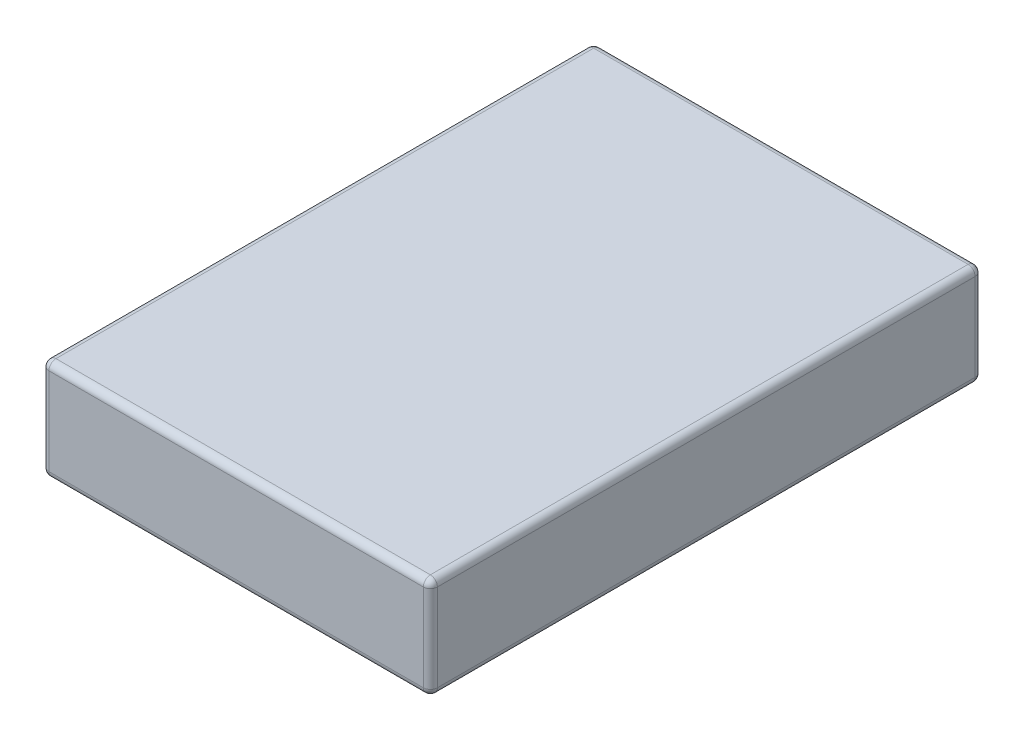
SolidWorks part; units mm, degrees
ref_plane "Ön Düzlem" through (0, 0, 0) normal (0, 0, 1) x (1, 0, 0)
ref_plane "Üst Düzlem" through (0, 0, 0) normal (0, 1, 0) x (1, 0, 0)
ref_plane "Sağ Düzlem" through (0, 0, 0) normal (1, 0, 0) x (0, 0, -1)
sketch "Sketch1" plane through (0, 0, 0) normal (0, 1, 0) x (1, 0, 0)
  line L1 (66.5, -98) -> (-66.5, -98)
  line L2 (69, -95.5) -> (69, 95.5)
  line L3 (66.5, 98) -> (-66.5, 98)
  line L4 (-69, -95.5) -> (-69, 95.5)
  line L5 (69, -98) -> (-69, 98) construction
  line L6 (69, 98) -> (-69, -98) construction
  arc A0 (-66.5, -98) -> (-69, -95.5) centre (-66.5, -95.5) cw
  arc A1 (66.5, -98) -> (69, -95.5) centre (66.5, -95.5) ccw
  arc A2 (69, 95.5) -> (66.5, 98) centre (66.5, 95.5) ccw
  arc A3 (-66.5, 98) -> (-69, 95.5) centre (-66.5, 95.5) ccw
  point P0 (0, 0)
  dimension "D3" = 2.5
  dimension "D1" = 138
  dimension "D2" = 196
extrude "Boss-Extrude1" add sketch "Sketch1" along normal blind 36
fillet "Fillet1" radius 2.5 16 edges at (0, 0, 98) (68.2678, 0, 97.2678) (69, 0, 0) (68.2678, 0, -97.2678) (0, 0, -98) (-68.2678, 0, -97.2678) (-69, 0, 0) (-68.2678, 0, 97.2678) (-69, 36, 0) (-68.2678, 36, -97.2678) (0, 36, -98) (68.2678, 36, -97.2678) (69, 36, 0) (68.2678, 36, 97.2678) (0, 36, 98) (-68.2678, 36, 97.2678)
